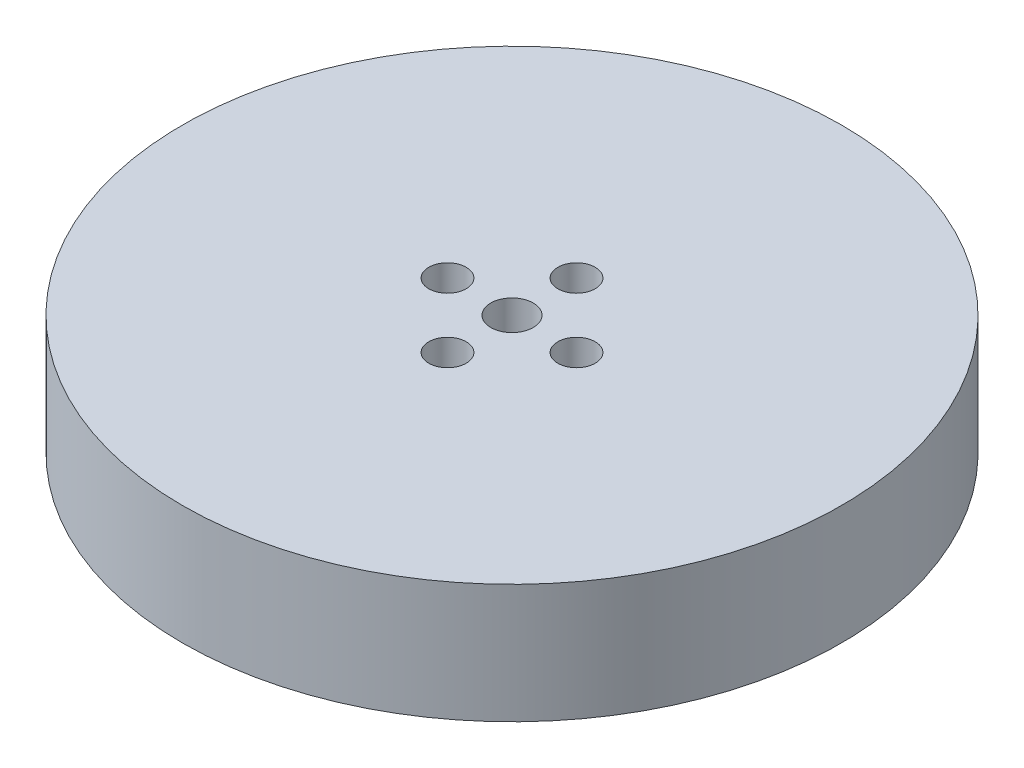
SolidWorks part; units mm, degrees
ref_plane "Front Plane" through (0, 0, 0) normal (0, 0, 1) x (1, 0, 0)
ref_plane "Top Plane" through (0, 0, 0) normal (0, 1, 0) x (1, 0, 0)
ref_plane "Right Plane" through (0, 0, 0) normal (1, 0, 0) x (0, 0, -1)
sketch "Sketch1" plane through (0, 0, 0) normal (0, 1, 0) x (1, 0, 0)
  circle A0 centre (0, 0) radius 77.5
  dimension "FLANGE_OD" = 155
extrude "Boss-Extrude1" add sketch "Sketch1" along normal blind 28
sketch "Sketch2" plane through (0, 0, 0) normal (0, 1, 0) x (1, 0, 0)
  circle A0 centre (0, 0) radius 5
  dimension "BORE_D" = 10
extrude "Cut-Extrude1" cut sketch "Sketch2" along normal through all
sketch "Sketch3" plane through (0, 28, 0) normal (0, 1, 0) x (1, 0, 0)
  circle A0 centre (0, 0) radius 15.1703 construction
  circle A1 centre (-15.1703, 0) radius 4.3938
  dimension "BOLT_D" = 8.7876
  dimension "BOLT_PCD" = 30.3407
extrude "Cut-Extrude2" cut sketch "Sketch3" against normal blind 20.5898
pattern_circular "CirPattern1" count 4 over 360 about axis through (0, 0, 0) along (0, 1, 0) of "Cut-Extrude2"
